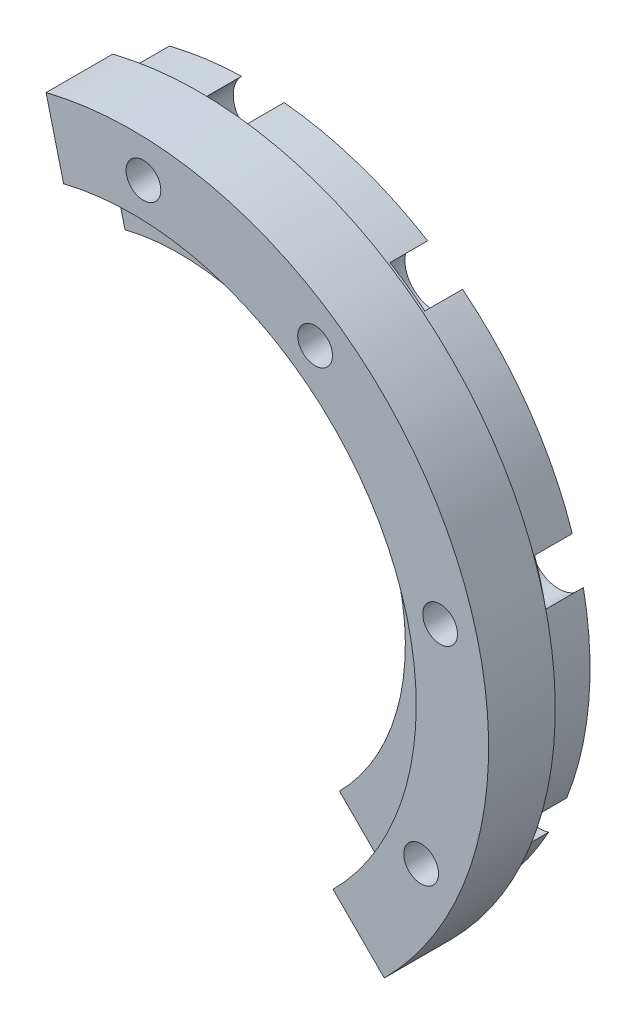
SolidWorks part; units mm, degrees
ref_plane "Front Plane" through (0, 0, 0) normal (0, 0, 1) x (1, 0, 0)
ref_plane "Top Plane" through (0, 0, 0) normal (0, 1, 0) x (1, 0, 0)
ref_plane "Right Plane" through (0, 0, 0) normal (1, 0, 0) x (0, 0, -1)
ref_plane "PZ_p24_600" through (0, 0, 24.6) normal (0, 0, 1) x (1, 0, 0)
sketch "S_prism1" plane through (0, 0, 24.6) normal (0, 0, 1) x (1, 0, 0)
  line L0 (-5.9513, 23.8693) -> (-4.7417, 19.0178)
  line L1 (13.8593, -13.8593) -> (17.3948, -17.3948)
  arc A0 (17.3948, -17.3948) -> (-5.9513, 23.8693) centre (0, 0) ccw
  arc A1 (-4.7417, 19.0178) -> (13.8593, -13.8593) centre (0, 0) cw
extrude "Boss_1" add sketch "S_prism1" along normal blind 5.6
ref_plane "PZ_p22_000" through (0, 0, 22) normal (0, 0, 1) x (1, 0, 0)
sketch "S_prism2" plane through (0, 0, 22) normal (0, 0, 1) x (1, 0, 0)
  line L0 (-5.6332, 22.7118) -> (-3.7555, 15.1412)
  line L1 (11.0443, -11.0174) -> (16.5665, -16.5261)
  arc A0 (16.5665, -16.5261) -> (-5.6332, 22.7118) centre (0, 0) ccw
  arc A1 (-3.7555, 15.1412) -> (11.0443, -11.0174) centre (0, 0) cw
extrude "Boss_2" add sketch "S_prism2" along normal blind 4.95
ref_plane "PZ_p24_500" through (0, 0, 24.5) normal (0, 0, 1) x (1, 0, 0)
sketch "S_pcut3" plane through (0, 0, 24.5) normal (0, 0, 1) x (1, 0, 0)
  line L0 (-6.4187, 23.955) -> (-6.0564, 22.6027)
  line L1 (16.255, -16.8326) -> (17.2275, -17.8396)
  arc A0 (17.2275, -17.8396) -> (-6.4187, 23.955) centre (0, 0) ccw
  arc A1 (-6.0564, 22.6027) -> (16.255, -16.8326) centre (0, 0) cw
extrude "Cut_3" cut sketch "S_pcut3" along normal blind 1.1
ref_plane "PZ_p21_900" through (0, 0, 21.9) normal (0, 0, 1) x (1, 0, 0)
sketch "S_hole4" plane through (0, 0, 21.9) normal (0, 0, 1) x (1, 0, 0)
  circle A0 centre (19.9388, -9.2976) radius 1.2
  dimension "D1_S_hole4" = 2.4
  dimension "P2" = 19.9388
  dimension "P3" = 9.2976
extrude "Hole_4" cut sketch "S_hole4" along normal blind 8.4
sketch "S_hole5" plane through (0, 0, 21.9) normal (0, 0, 1) x (1, 0, 0)
  circle A0 centre (19.9388, -9.2976) radius 2
  dimension "D1_S_hole5" = 4
  dimension "P2" = 19.9388
  dimension "P3" = 9.2976
extrude "Hole_5" cut sketch "S_hole5" along normal blind 2.7
sketch "S_hole6" plane through (0, 0, 21.9) normal (0, 0, 1) x (1, 0, 0)
  circle A0 centre (21.2504, 5.694) radius 1.2
  dimension "D1_S_hole6" = 2.4
  dimension "P2" = 21.2504
  dimension "P3" = 5.694
extrude "Hole_6" cut sketch "S_hole6" along normal blind 8.4
sketch "S_hole7" plane through (0, 0, 21.9) normal (0, 0, 1) x (1, 0, 0)
  circle A0 centre (21.2504, 5.694) radius 2
  dimension "D1_S_hole7" = 4
  dimension "P2" = 21.2504
  dimension "P3" = 5.694
extrude "Hole_7" cut sketch "S_hole7" along normal blind 2.7
sketch "S_hole8" plane through (0, 0, 21.9) normal (0, 0, 1) x (1, 0, 0)
  circle A0 centre (12.6187, 18.0213) radius 1.2
  dimension "D1_S_hole8" = 2.4
  dimension "P2" = 12.6187
  dimension "P3" = 18.0213
extrude "Hole_8" cut sketch "S_hole8" along normal blind 8.4
sketch "S_hole9" plane through (0, 0, 21.9) normal (0, 0, 1) x (1, 0, 0)
  circle A0 centre (12.6187, 18.0213) radius 2
  dimension "D1_S_hole9" = 4
  dimension "P2" = 12.6187
  dimension "P3" = 18.0213
extrude "Hole_9" cut sketch "S_hole9" along normal blind 2.7
sketch "S_hole10" plane through (0, 0, 21.9) normal (0, 0, 1) x (1, 0, 0)
  circle A0 centre (0.7678, 21.9866) radius 1.2
  dimension "D1_S_hole10" = 2.4
  dimension "P2" = 0.7678
  dimension "P3" = 21.9866
extrude "Hole_10" cut sketch "S_hole10" along normal blind 8.4
sketch "S_hole11" plane through (0, 0, 21.9) normal (0, 0, 1) x (1, 0, 0)
  circle A0 centre (0.7678, 21.9866) radius 2
  dimension "D1_S_hole11" = 4
  dimension "P2" = 0.7678
  dimension "P3" = 21.9866
extrude "Hole_11" cut sketch "S_hole11" along normal blind 2.7
equation "\"plate_t\" = 3"
equation "\"clearance\" = 0.4"
